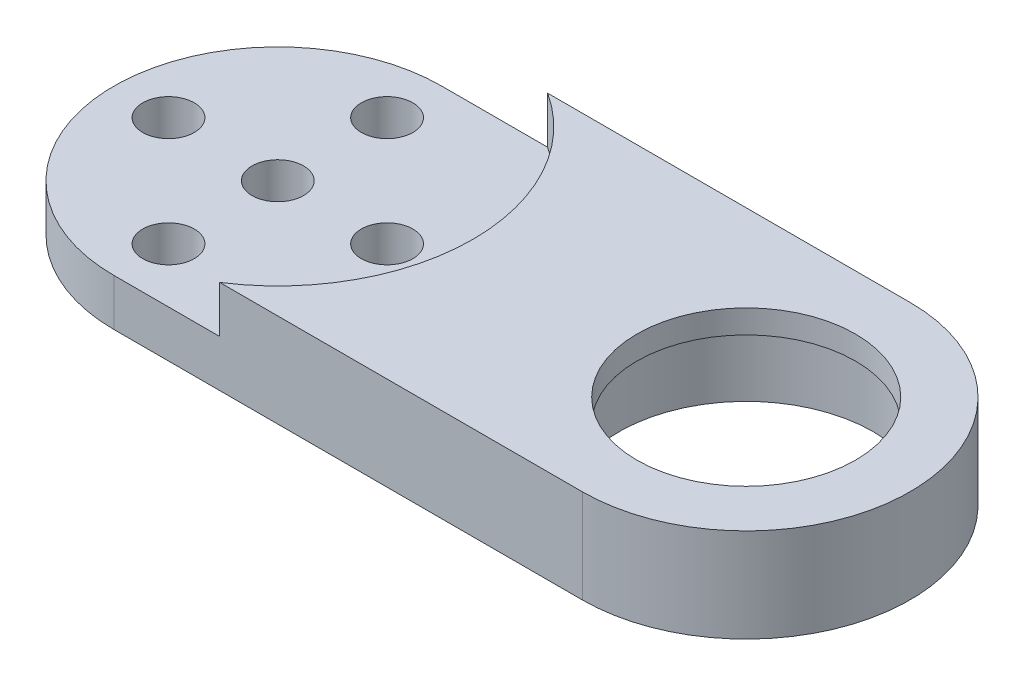
SolidWorks part; units mm, degrees
ref_plane "Front Plane" through (0, 0, 0) normal (0, 0, 1) x (1, 0, 0)
ref_plane "Top Plane" through (0, 0, 0) normal (0, 1, 0) x (1, 0, 0)
ref_plane "Right Plane" through (0, 0, 0) normal (1, 0, 0) x (0, 0, -1)
sketch "Sketch2" plane through (0, 0, 0) normal (0, 1, 0) x (1, 0, 0)
  line L0 (15, 0) -> (-15, 0) construction
  line L1 (15, 10.5) -> (-15, 10.5)
  line L2 (15, -10.5) -> (-15, -10.5)
  arc A0 (15, 10.5) -> (15, -10.5) centre (15, 0) cw
  arc A1 (-15, 10.5) -> (-15, -10.5) centre (-15, 0) ccw
  point P4 (0, 0)
  dimension "D1" = 30
  dimension "D2" = 10.5
  dimension "D3" = 10.5
extrude "Boss-Extrude1" add sketch "Sketch2" along normal blind 6
sketch "Sketch4" plane through (0, 6, 0) normal (0, 1, 0) x (1, 0, 0)
  line L0 (-15, 0) -> (-8, 0) construction
  line L1 (15, 0) -> (-15, 0) construction
  line L2 (-15, 0) -> (-8, 0) construction
  circle A0 centre (-15, 0) radius 1.65
  circle A1 centre (-8, 0) radius 1.65
  circle A2 centre (-15, -7) radius 1.65
  circle A3 centre (-22, 0) radius 1.65
  circle A4 centre (-15, 7) radius 1.65
  dimension "D1" = 3.3
  dimension "D2" = 7
  dimension "D3" = 4
extrude "Servo horn holes" cut sketch "Sketch4" against normal through all
sketch "Sketch5" plane through (0, 0, 0) normal (0, -1, 0) x (-1, 0, 0)
  circle A0 centre (-15, 0) radius 8.15
  dimension "D1" = 16.3
extrude "Bearing press fit" cut sketch "Sketch5" against normal blind 4.5
sketch "Sketch6" plane through (0, 6, 0) normal (0, 1, 0) x (1, 0, 0)
  circle A0 centre (15, 0) radius 10.5
  circle A1 centre (15, 0) radius 7
  dimension "D1" = 14
extrude "Boss-Extrude2" [suppressed] add sketch "Sketch6" along normal blind 2
sketch "Sketch7" plane through (0, 6, 0) normal (0, 1, 0) x (1, 0, 0)
  circle A0 centre (-15, 0) radius 12.5
  dimension "D1" = 25
extrude "Cut-Extrude1" cut sketch "Sketch7" against normal blind 3
sketch "Sketch8" plane through (0, 4.5, 0) normal (0, -1, 0) x (1, 0, 0)
  circle A0 centre (15, 0) radius 7
  dimension "D1" = 14
extrude "Cut-Extrude2" cut sketch "Sketch8" against normal through all
